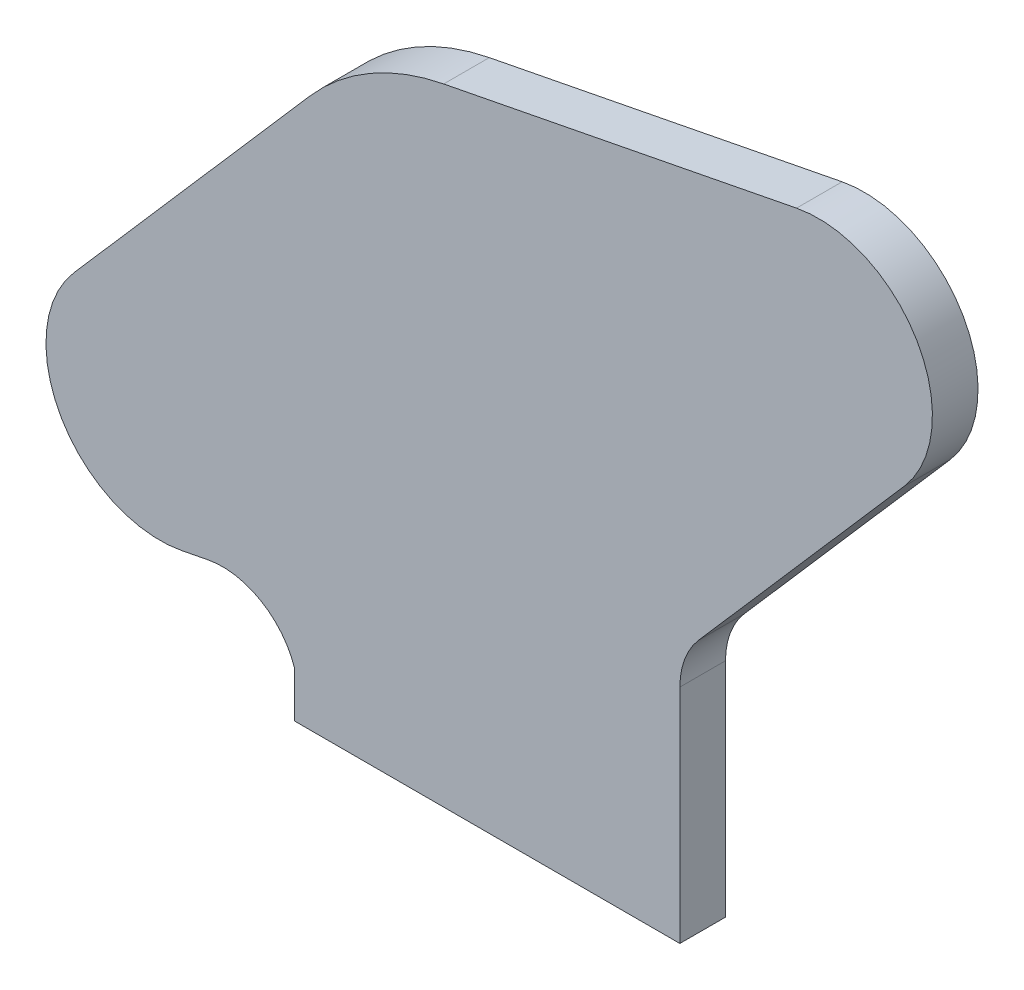
SolidWorks part; units mm, degrees
ref_plane "Front Plane" through (0, 0, 0) normal (0, 0, 1) x (1, 0, 0)
ref_plane "Top Plane" through (0, 0, 0) normal (0, 1, 0) x (1, 0, 0)
ref_plane "Right Plane" through (0, 0, 0) normal (1, 0, 0) x (0, 0, -1)
sketch "Sketch1" plane through (0, 0, 0) normal (0, 0, 1) x (1, 0, 0)
  line L0 (-8.1242, -16.4211) -> (-6.3754, -16.4211)
  line L1 (6.3754, -16.4211) -> (7.9629, -16.4211)
  line L11 (6.8834, -24.6761) -> (7.9629, -24.6761)
  line L12 (7.9629, -24.6761) -> (7.9629, -7.1478)
  line L13 (8.7434, -5.0629) -> (17.3399, 4.8101)
  line L14 (12.8356, 12.6118) -> (-1.9005, 9.7349)
  line L15 (-7.4804, 6.5133) -> (-17.3399, -4.8101)
  line L16 (-12.8356, -12.6118) -> (-11.7463, -12.3991)
  line L17 (-8.1242, -14.5161) -> (-8.1242, -24.6761)
  line L18 (-8.1242, -24.6761) -> (-6.8834, -24.6761)
  line L19 (6.8834, -6.1404) -> (6.8834, -24.6761)
  line L22 (7.9629, -16.4211) -> (7.9629, -7.1478)
  line L23 (8.7434, -5.0629) -> (17.3399, 4.8101)
  line L24 (12.8356, 12.6118) -> (-1.9005, 9.7349)
  line L25 (-7.4804, 6.5133) -> (-17.3399, -4.8101)
  line L26 (-12.8356, -12.6118) -> (-11.7463, -12.3991)
  line L27 (-8.1242, -14.5161) -> (-8.1242, -16.4211)
  line L42 (6.8834, -6.1404) -> (6.8834, -24.6761)
  line L43 (-6.8834, -24.6761) -> (-6.8834, -6.1404)
  line L44 (-6.8834, -24.6761) -> (-6.8834, -6.1404)
  circle A0 centre (13.7482, 7.9375) radius 2.6162 construction
  circle A1 centre (-13.7482, -7.9375) radius 2.6162 construction
  circle A2 centre (13.7482, 7.9375) radius 2.6162
  circle A3 centre (-13.7482, -7.9375) radius 2.6162
  arc A8 (7.2109, -5.1121) -> (6.8834, -6.1404) centre (8.6614, -6.1404) ccw
  arc A9 (8.7434, -5.0629) -> (7.9629, -7.1478) centre (11.1379, -7.1478) ccw
  arc A10 (17.3399, 4.8101) -> (12.8356, 12.6118) centre (13.7482, 7.9375) ccw
  arc A11 (-1.9005, 9.7349) -> (-7.4804, 6.5133) centre (0, 0) ccw
  arc A12 (-17.3399, -4.8101) -> (-12.8356, -12.6118) centre (-13.7482, -7.9375) ccw
  arc A13 (-8.1242, -14.5161) -> (-11.7463, -12.3991) centre (-11.1379, -15.5153) ccw
  arc A14 (7.2109, -5.1121) -> (6.8834, -6.1404) centre (8.6614, -6.1404) ccw
  arc A15 (-6.8834, -6.1404) -> (-7.2109, -5.1121) centre (-8.6614, -6.1404) ccw
  arc A17 (8.7434, -5.0629) -> (7.9629, -7.1478) centre (11.1379, -7.1478) ccw
  arc A18 (17.3399, 4.8101) -> (12.8356, 12.6118) centre (13.7482, 7.9375) ccw
  arc A19 (-1.9005, 9.7349) -> (-7.4804, 6.5133) centre (0, 0) ccw
  arc A20 (-17.3399, -4.8101) -> (-12.8356, -12.6118) centre (-13.7482, -7.9375) ccw
  arc A21 (-8.1242, -14.5161) -> (-11.7463, -12.3991) centre (-11.1379, -15.5153) ccw
  arc A36 (-6.8834, -6.1404) -> (-7.2109, -5.1121) centre (-8.6614, -6.1404) ccw
  arc A37 (7.2109, -5.1121) -> (-7.2109, -5.1121) centre (0, 0) ccw
  arc A38 (7.2109, -5.1121) -> (-7.2109, -5.1121) centre (0, 0) ccw
  dimension "D2" = 1.905
  dimension "D1" = 0
extrude "Boss-Extrude1" add sketch "Sketch1" along normal blind 0.762 rebuild error yes
sketch "Sketch2" plane through (0, 0, 0.762) normal (0, 0, 1) x (1, 0, 0)
  line L0 (-6.3754, -16.4211) -> (6.3754, -16.4211)
  line L10 (-8.1242, -14.5161) -> (-8.1242, -16.4211)
  line L11 (-8.1242, -16.4211) -> (-6.3754, -16.4211)
  line L12 (-6.3754, -16.4211) -> (-6.3754, -6.1404)
  line L13 (6.3754, -6.1404) -> (6.3754, -16.4211)
  line L14 (6.3754, -16.4211) -> (7.9629, -16.4211)
  line L15 (7.9629, -16.4211) -> (7.9629, -7.1478)
  line L16 (8.7434, -5.0629) -> (17.3399, 4.8101)
  line L17 (12.8356, 12.6118) -> (-1.9005, 9.7349)
  line L18 (-7.4804, 6.5133) -> (-17.3399, -4.8101)
  line L19 (-12.8356, -12.6118) -> (-11.7463, -12.3991)
  line L20 (-8.1242, -14.5161) -> (-8.1242, -16.4211)
  line L21 (-8.1242, -16.4211) -> (-6.3754, -16.4211)
  line L24 (6.3754, -16.4211) -> (7.9629, -16.4211)
  line L25 (7.9629, -16.4211) -> (7.9629, -7.1478)
  line L26 (8.7434, -5.0629) -> (17.3399, 4.8101)
  line L27 (12.8356, 12.6118) -> (-1.9005, 9.7349)
  line L28 (-7.4804, 6.5133) -> (-17.3399, -4.8101)
  line L29 (-12.8356, -12.6118) -> (-11.7463, -12.3991)
  arc A8 (-6.3754, -6.1404) -> (-6.7965, -4.8183) centre (-8.6614, -6.1404) ccw
  arc A9 (6.7965, -4.8183) -> (-6.7965, -4.8183) centre (0, 0) ccw
  arc A10 (6.7965, -4.8183) -> (6.3754, -6.1404) centre (8.6614, -6.1404) ccw
  arc A11 (8.7434, -5.0629) -> (7.9629, -7.1478) centre (11.1379, -7.1478) ccw
  arc A12 (17.3399, 4.8101) -> (12.8356, 12.6118) centre (13.7482, 7.9375) ccw
  arc A13 (-1.9005, 9.7349) -> (-7.4804, 6.5133) centre (0, 0) ccw
  arc A14 (-17.3399, -4.8101) -> (-12.8356, -12.6118) centre (-13.7482, -7.9375) ccw
  arc A15 (-8.1242, -14.5161) -> (-11.7463, -12.3991) centre (-11.1379, -15.5153) ccw
  arc A19 (8.7434, -5.0629) -> (7.9629, -7.1478) centre (11.1379, -7.1478) ccw
  arc A20 (17.3399, 4.8101) -> (12.8356, 12.6118) centre (13.7482, 7.9375) ccw
  arc A21 (-1.9005, 9.7349) -> (-7.4804, 6.5133) centre (0, 0) ccw
  arc A22 (-17.3399, -4.8101) -> (-12.8356, -12.6118) centre (-13.7482, -7.9375) ccw
  arc A23 (-8.1242, -14.5161) -> (-11.7463, -12.3991) centre (-11.1379, -15.5153) ccw
  dimension "D1" = 0
extrude "Boss-Extrude2" add sketch "Sketch2" along normal blind 1.905
